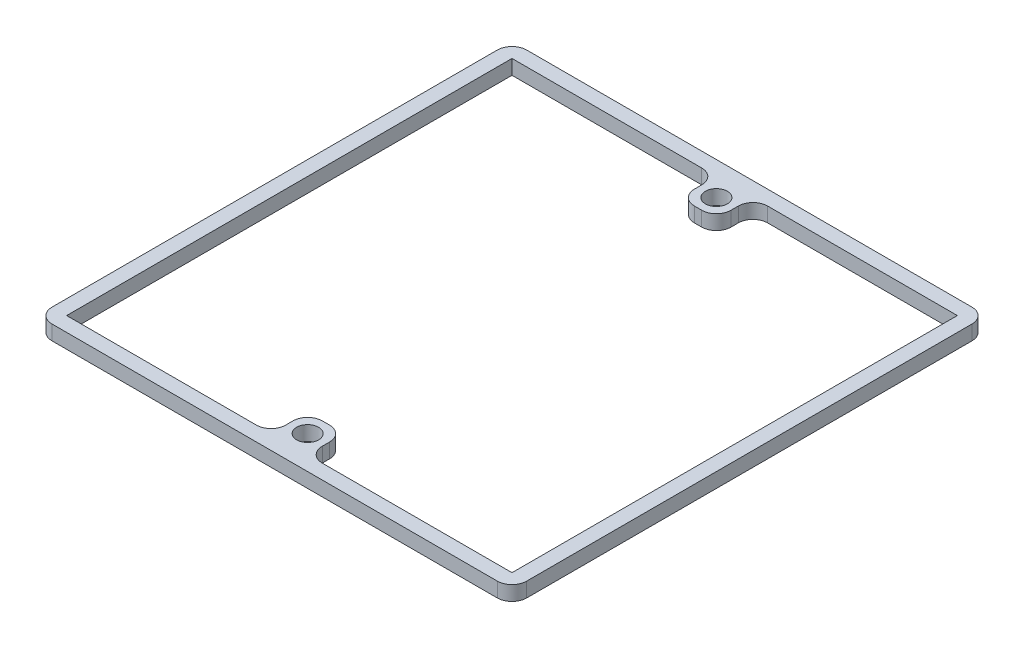
SolidWorks part; units mm, degrees
ref_plane "Front Plane" through (0, 0, 0) normal (0, 0, 1) x (1, 0, 0)
ref_plane "Top Plane" through (0, 0, 0) normal (0, 1, 0) x (1, 0, 0)
ref_plane "Right Plane" through (0, 0, 0) normal (1, 0, 0) x (0, 0, -1)
sketch "Sketch1" plane through (0, 0, 0) normal (0, 1, 0) x (1, 0, 0)
  line L0 (30.425, -30.425) -> (30.425, 30.425)
  line L1 (32.425, -32.425) -> (-32.425, -32.425)
  line L2 (32.425, -32.425) -> (32.425, 32.425)
  line L3 (32.425, 32.425) -> (-32.425, 32.425)
  line L4 (-32.425, -32.425) -> (-32.425, 32.425)
  line L5 (32.425, -32.425) -> (-32.425, 32.425) construction
  line L6 (32.425, 32.425) -> (-32.425, -32.425) construction
  line L7 (30.425, 30.425) -> (-30.425, 30.425)
  line L8 (-30.425, -30.425) -> (-30.425, 30.425)
  line L9 (30.425, -30.425) -> (-30.425, -30.425)
  point P0 (0, 0)
  dimension "D2" = 64.85
  dimension "D3" = 2
extrude "Boss-Extrude1" add sketch "Sketch1" along normal blind 2
sketch "Sketch2" plane through (0, 2, 0) normal (0, 1, 0) x (1, 0, 0)
  line L0 (30.425, 30.425) -> (-30.425, 30.425) construction
  line L1 (30.425, 30.425) -> (-30.425, 30.425)
  line L2 (0, 30.425) -> (0, -30.425) construction
  line L3 (-2.5, 30.425) -> (2.5, 30.425)
  line L4 (32.425, -32.425) -> (32.425, 32.425)
  line L5 (32.425, 32.425) -> (-32.425, 32.425)
  line L6 (-32.425, 32.425) -> (-32.425, -32.425)
  line L7 (-32.425, -32.425) -> (32.425, -32.425)
  line L8 (32.425, -32.425) -> (32.425, 32.425)
  line L9 (32.425, 32.425) -> (-32.425, 32.425)
  line L10 (-32.425, 32.425) -> (-32.425, -32.425)
  line L11 (-32.425, -32.425) -> (32.425, -32.425)
  line L12 (-2.5, 30.425) -> (-2.5, 25.425)
  line L13 (-2.5, 25.425) -> (2.5, 25.425)
  line L14 (2.5, 30.425) -> (2.5, 25.425)
  line L15 (-30.425, -30.425) -> (30.425, -30.425) construction
  line L16 (-30.425, 0) -> (30.425, 0) construction
  line L17 (-30.425, 30.425) -> (-30.425, -30.425) construction
  line L18 (30.425, -30.425) -> (30.425, 30.425) construction
  line L19 (2.5, -30.425) -> (2.5, -25.425)
  line L20 (-2.5, -30.425) -> (2.5, -30.425)
  line L21 (-2.5, -30.425) -> (-2.5, -25.425)
  line L22 (-2.5, -25.425) -> (2.5, -25.425)
  circle A0 centre (0, 27.925) radius 1.5
  circle A1 centre (0, -27.925) radius 1.5
  point P20 (0, 25.425)
  point P34 (-2.5, 27.925)
  line M29 (30.425, -30.425) -> (-30.425, -30.425)
  dimension "D4" = 3
  dimension "D3" = 5
extrude "Boss-Extrude2" add sketch "Sketch2" against normal up to surface (2 mm away) contours L14 L1 L12 L13 A0 | L22 L21 L19 A1 M29 region at (2.4293, 2, -27.925) region at (0, 2, 30.3543) up to face at (0, 0, 0)
fillet "Fillet1" radius 2 12 edges at (32.425, 1, -32.425) (32.425, 1, 32.425) (-32.425, 1, 32.425) (-32.425, 1, -32.425) (-2.5, 1, 25.425) (2.5, 1, 25.425) (2.5, 1, -25.425) (-2.5, 1, -25.425) (-2.5, 1, 30.425) (2.5, 1, 30.425) (2.5, 1, -30.425) (-2.5, 1, -30.425)
sketch "Sketch3" [suppressed] plane through (0, 2, 0) normal (0, 1, 0) x (1, 0, 0)
  line L0 (-4.5, 22.925) -> (-22.925, 22.925) construction
  line L1 (-14, 22.925) -> (-6, 22.925)
  line L2 (-14, 22.925) -> (-14, 16.925)
  line L3 (-14, 16.925) -> (-6, 16.925)
  line L4 (24.925, -22.925) -> (24.925, 22.925)
  line L5 (22.925, 24.925) -> (-22.925, 24.925)
  line L6 (-24.925, 22.925) -> (-24.925, -22.925)
  line L7 (-22.925, -24.925) -> (22.925, -24.925)
  line L8 (24.925, -22.925) -> (24.925, 22.925)
  line L9 (22.925, 24.925) -> (-22.925, 24.925)
  line L10 (-24.925, 22.925) -> (-24.925, -22.925)
  line L11 (-22.925, -24.925) -> (22.925, -24.925)
  line L12 (-6, 22.925) -> (-6, 16.925)
  circle A0 centre (0, 20.425) radius 1.5 construction
  circle A1 centre (0, 20.425) radius 1.5
  circle A2 centre (-10, 20.425) radius 2.3813
  arc A4 (24.925, 22.925) -> (22.925, 24.925) centre (22.925, 22.925) ccw
  arc A5 (-22.925, 24.925) -> (-24.925, 22.925) centre (-22.925, 22.925) ccw
  arc A6 (-24.925, -22.925) -> (-22.925, -24.925) centre (-22.925, -22.925) ccw
  arc A7 (22.925, -24.925) -> (24.925, -22.925) centre (22.925, -22.925) ccw
  arc A8 (24.925, 22.925) -> (22.925, 24.925) centre (22.925, 22.925) ccw
  arc A9 (-22.925, 24.925) -> (-24.925, 22.925) centre (-22.925, 22.925) ccw
  arc A10 (-24.925, -22.925) -> (-22.925, -24.925) centre (-22.925, -22.925) ccw
  arc A11 (22.925, -24.925) -> (24.925, -22.925) centre (22.925, -22.925) ccw
  point P23 (-10, 22.925)
  line M29 (-22.925, 22.925) -> (-4.5, 22.925)
  dimension "D2" = 4.7625
  dimension "D3" = 8
  dimension "D4" = 6
  dimension "D5" = 10
extrude "Boss-Extrude3" [suppressed] add sketch "Sketch3" against normal up to surface (2 mm away) contours L12 L2 L3 A2 M29 up to face at (0, 0, 0)
fillet "Fillet2" [suppressed] radius 2
equation "\"D\"= 65"
equation "\"D2@Sketch1\"=\"D\"-\"C\""
equation "\"T\"=2"
equation "\"D3@Sketch1\"=\"T\""
equation "\"D1@Boss-Extrude1\"=\"T\""
equation "\"F\"=2"
equation "\"D1@Fillet1\"=\"F\""
equation "\"TAB\"=5"
equation "\"D2@Sketch2\"=\"TAB\""
equation "\"D3@Sketch2\"=\"TAB\""
equation "\"TABH\"=3"
equation "\"D4@Sketch2\"=\"TABH\""
equation "\"C\"= 0.15"
equation "\"OUTPUTTUBE\"=4.7625"
equation "\"D2@Sketch3\"=\"OUTPUTTUBE\""
equation "\"OUTPUTL\"= 8"
equation "\"D3@Sketch3\"=\"OUTPUTL\""
equation "\"OUTPUTW\"= 6"
equation "\"D4@Sketch3\"=\"OUTPUTW\""
equation "\"D1@Fillet2\"=\"F\""
